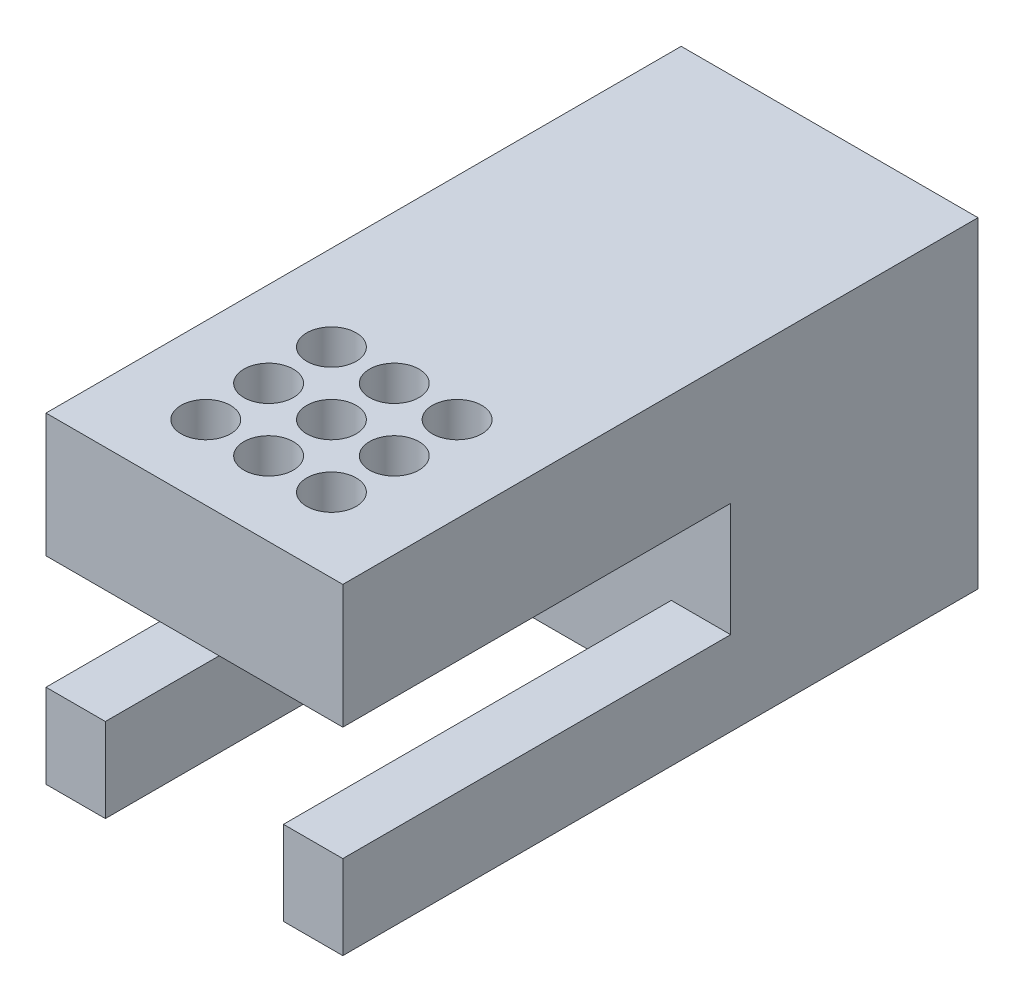
SolidWorks part; units mm, degrees
ref_plane "Front Plane" through (0, 0, 0) normal (0, 0, 1) x (1, 0, 0)
ref_plane "Top Plane" through (0, 0, 0) normal (0, 1, 0) x (1, 0, 0)
ref_plane "Right Plane" through (0, 0, 0) normal (1, 0, 0) x (0, 0, -1)
sketch "Sketch1" plane through (0, 0, 0) normal (0, 1, 0) x (1, 0, 0)
  line L0 (-2.54, 0) -> (2.54, 0) construction
  line L1 (-6, 10.14) -> (6, 10.14)
  line L2 (-6, 10.14) -> (-6, -5.54)
  line L3 (-6, -5.54) -> (6, -5.54)
  line L4 (6, 10.14) -> (6, -5.54)
  line L5 (0, 10.14) -> (0, 0) construction
  line L9 (-2.54, -2.54) -> (2.54, -2.54) construction
  line L10 (-6, 10.14) -> (6, 10.14)
  line L11 (-6, 10.14) -> (-6, 20.14)
  line L12 (-6, 20.14) -> (6, 20.14)
  line L13 (6, 10.14) -> (6, 20.14)
  line L14 (-6, 10.14) -> (6, 20.14) construction
  line L15 (-6, 20.14) -> (6, 10.14) construction
  circle A0 centre (-2.54, 0) radius 1
  circle A1 centre (0, 0) radius 1
  circle A2 centre (2.54, 0) radius 1
  circle A3 centre (2.54, -2.54) radius 1
  circle A4 centre (0, -2.54) radius 1
  circle A5 centre (-2.54, -2.54) radius 1
  circle A6 centre (-2.54, 2.54) radius 1
  circle A7 centre (0, 2.54) radius 1
  circle A8 centre (2.54, 2.54) radius 1
  point P4 (0, 0)
  point P5 (0, -2.54)
  point P13 (0, 0)
  point P26 (0, 15.14)
  dimension "D5" = 2
  dimension "D1" = 7.6
  dimension "D2" = 12
  dimension "D3" = 5.08
  dimension "D4" = 2.54
  dimension "D6" = 10
  dimension "D7" = 3
  dimension "D8" = 2.54
extrude "Boss-Extrude1" add sketch "Sketch1" along normal blind 5 contours L4 L1 L2 L3 A5 A4 A3 A2 A1 A0 | L1 L13 L12 L11 region at (0, 0, -15.14) region at (0, 0, -9.9426)
extrude "Boss-Extrude2" add sketch "Sketch1<3>" against normal blind 8 contours L1 L13 L12 L11 region at (0, 0, -15.14)
sketch "Sketch1<3>" plane through (0, 0, 0) normal (0, 1, 0) x (1, 0, 0) same geometry as "Sketch1"
sketch "Sketch2" plane through (0, 0, -10.14) normal (0, 0, 1) x (1, 0, 0)
  line L0 (-6, 0) -> (6, 0) construction
  line L1 (-6, -8) -> (-3.6, -8)
  line L2 (-6, -8) -> (-6, -4.6)
  line L3 (-6, -4.6) -> (-3.6, -4.6)
  line L4 (-3.6, -8) -> (-3.6, -4.6)
  line L5 (-6, -8) -> (-3.6, -4.6) construction
  line L6 (-6, -4.6) -> (-3.6, -8) construction
  line L7 (6, -8) -> (3.6, -8)
  line L8 (6, -8) -> (6, -4.6)
  line L9 (6, -4.6) -> (3.6, -4.6)
  line L10 (3.6, -8) -> (3.6, -4.6)
  line L11 (6, -8) -> (3.6, -4.6) construction
  line L12 (6, -4.6) -> (3.6, -8) construction
  point P4 (-4.8, -6.3)
  point P10 (4.8, -6.3)
  dimension "D1" = 4.6
  dimension "D2" = 7.2
extrude "Boss-Extrude3" add sketch "Sketch2" along normal up to surface (15.68 mm away) up to face at (0, 2.5, 5.54)
equation "\"13.46 \"=18.6309"
equation "\"13.46 mm\"=18.6309"
